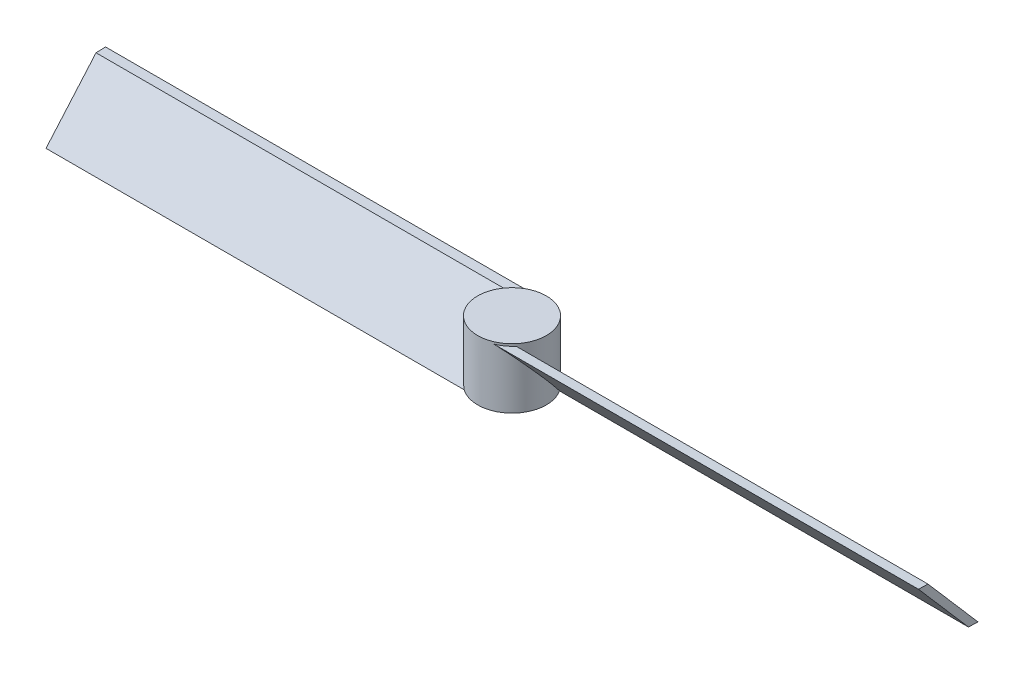
SolidWorks part; units mm, degrees
ref_plane "Front Plane" through (0, 0, 0) normal (0, 0, 1) x (1, 0, 0)
ref_plane "Top Plane" through (0, 0, 0) normal (0, 1, 0) x (1, 0, 0)
ref_plane "Right Plane" through (0, 0, 0) normal (1, 0, 0) x (0, 0, -1)
sketch "Sketch1" plane through (0, 0, 0) normal (0, 1, 0) x (1, 0, 0)
  circle A0 centre (0, 0) radius 2
extrude "Boss-Extrude1" add sketch "Sketch1" along normal blind 3.5
sketch "Sketch2" plane through (0, 0, 0) normal (0, 1, 0) x (1, 0, 0)
  circle A0 centre (0, 0) radius 0.42
extrude "Cut-Extrude1" cut sketch "Sketch2" along normal blind 2.5
sketch "Sketch3" plane through (0, 0, 0) normal (1, 0, 0) x (0, 0, -1)
  line L0 (1.6275, 0) -> (-1.2839, 3.3629)
  line L1 (1.6275, 0) -> (1.0729, 0.0168)
  line L2 (-1.2839, 3.3629) -> (-1.8386, 3.3798)
  line L3 (1.0729, 0.0168) -> (-1.8386, 3.3798)
extrude "Boss-Extrude2" add sketch "Sketch3" along normal blind 25.5
sketch "Sketch4" plane through (0, 0, 0) normal (-1, 0, 0) x (0, 0, 1)
  line L0 (1.6275, 0) -> (-1.2839, 3.3629)
  line L1 (1.6275, 0) -> (1.0729, 0.0168)
  line L2 (-1.2839, 3.3629) -> (-1.8386, 3.3798)
  line L3 (1.0729, 0.0168) -> (-1.8386, 3.3798)
extrude "Boss-Extrude3" add sketch "Sketch4" along normal blind 25.5
